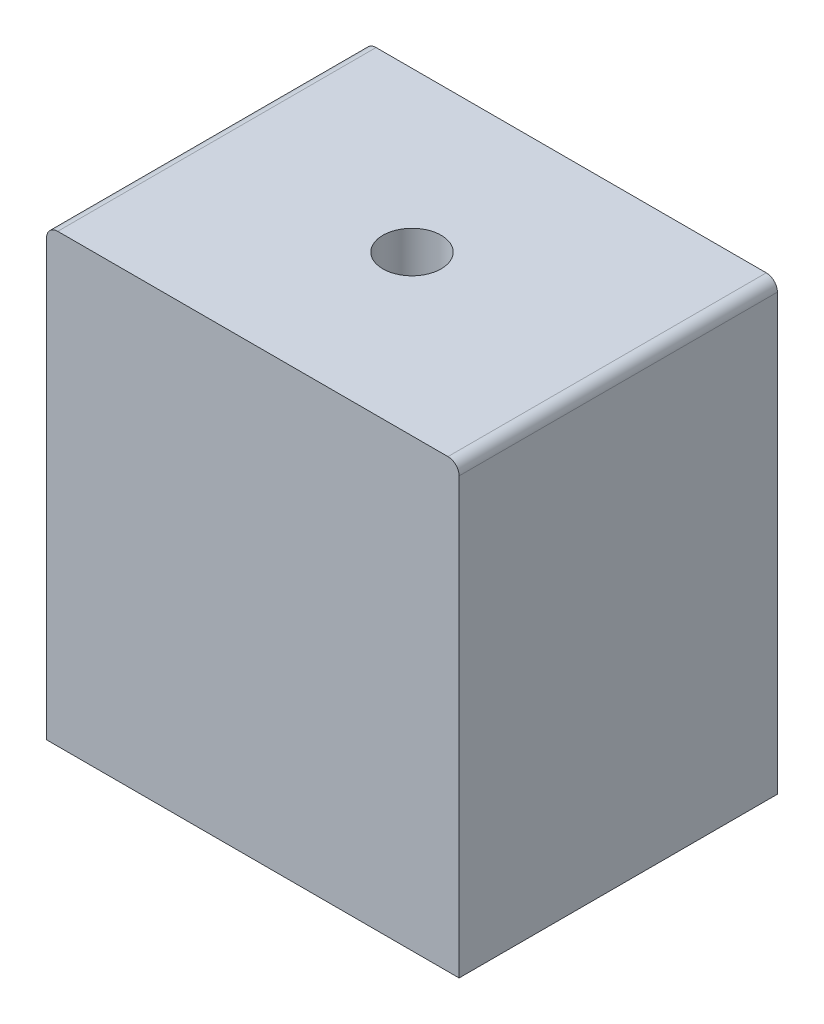
SolidWorks part; units mm, degrees
material "K110"
ref_plane "Front Plane" through (0, 0, 0) normal (0, 0, 1) x (1, 0, 0)
ref_plane "Top Plane" through (0, 0, 0) normal (0, 1, 0) x (1, 0, 0)
ref_plane "Right Plane" through (0, 0, 0) normal (1, 0, 0) x (0, 0, -1)
sketch "Sketch1" plane through (0, 0, 0) normal (0, 1, 0) x (1, 0, 0)
  line L1 (-37, -28.55) -> (37, -28.55)
  line L2 (-37, -28.55) -> (-37, 28.55)
  line L3 (-37, 28.55) -> (37, 28.55)
  line L4 (37, -28.55) -> (37, 28.55)
  line L5 (-37, -28.55) -> (37, 28.55) construction
  line L6 (-37, 28.55) -> (37, -28.55) construction
  point P0 (0, 0)
  dimension "D1" = 74
  dimension "D2" = 57.1
extrude "Boss-Extrude1" add sketch "Sketch1" along normal blind 80
fillet "Fillet1" radius 2 2 edges at (-37, 80, 0) (37, 80, 0)
sketch "Sketch2" plane through (0, 80, 0) normal (0, 1, 0) x (1, 0, 0)
  circle A0 centre (0, 0) radius 5.23
  dimension "D1" = 10.46
extrude "Cut-Extrude1" cut sketch "Sketch2" against normal up to next
